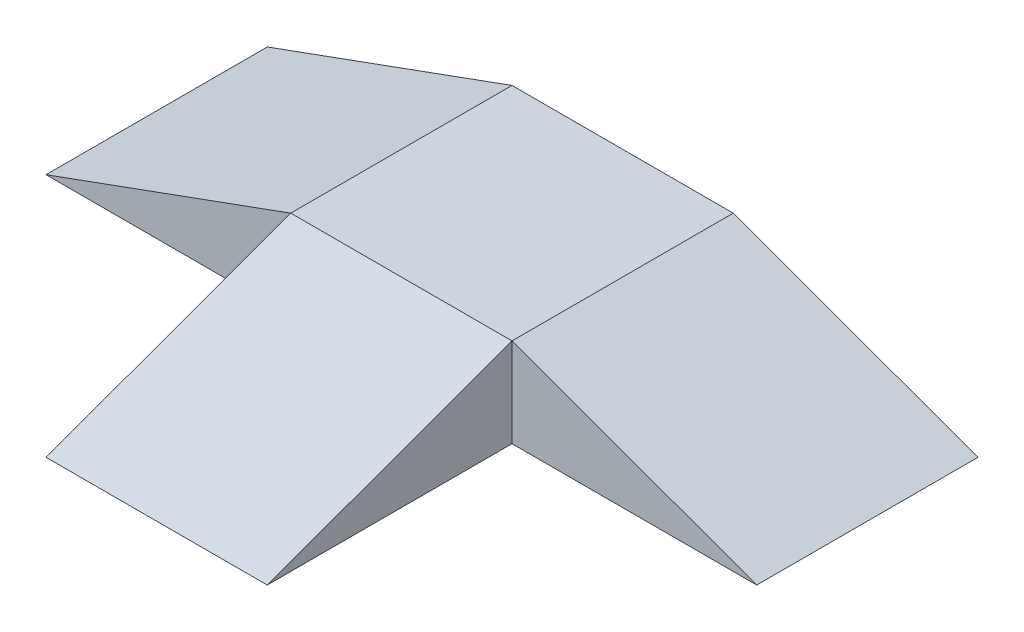
SolidWorks part; units mm, degrees
ref_plane "Front Plane" through (0, 0, 0) normal (0, 0, 1) x (1, 0, 0)
ref_plane "Top Plane" through (0, 0, 0) normal (0, 1, 0) x (1, 0, 0)
ref_plane "Right Plane" through (0, 0, 0) normal (1, 0, 0) x (0, 0, -1)
sketch "Sketch1" plane through (0, 0, 0) normal (0, 1, 0) x (1, 0, 0)
  line L1 (-175, -175) -> (175, -175)
  line L2 (-175, -175) -> (-175, 175)
  line L3 (-175, 175) -> (175, 175)
  line L4 (175, -175) -> (175, 175)
  line L5 (-175, -175) -> (175, 175) construction
  line L6 (-175, 175) -> (175, -175) construction
  point P0 (0, 0)
  dimension "D1" = 350
  dimension "D2" = 350
extrude "Boss-Extrude1" add sketch "Sketch1" along normal blind 140.9
sketch "Sketch2" plane through (0, 0, 0) normal (1, 0, 0) x (0, 0, -1)
  line L0 (-175, 140.9) -> (-175, 0)
  line L1 (-175, 0) -> (-562.1578, 0)
  line L2 (-562.1578, 0) -> (-175, 140.9)
  dimension "D1" = 412
extrude "Boss-Extrude2" add sketch "Sketch2" along normal mid plane 350
sketch "Sketch3" plane through (0, 0, 0) normal (0, 0, 1) x (1, 0, 0)
  line L0 (-175, 140.9) -> (-562.1578, 0)
  line L1 (-562.1578, 0) -> (-175, 0)
  line L2 (-175, 0) -> (-175, 140.9)
  line L3 (175, 140.9) -> (175, 0)
  line L4 (175, 0) -> (562.1578, 0)
  line L5 (562.1578, 0) -> (175, 140.9)
  dimension "D1" = 412
  dimension "D2" = 412
extrude "Boss-Extrude3" add sketch "Sketch3" along normal mid plane 350
